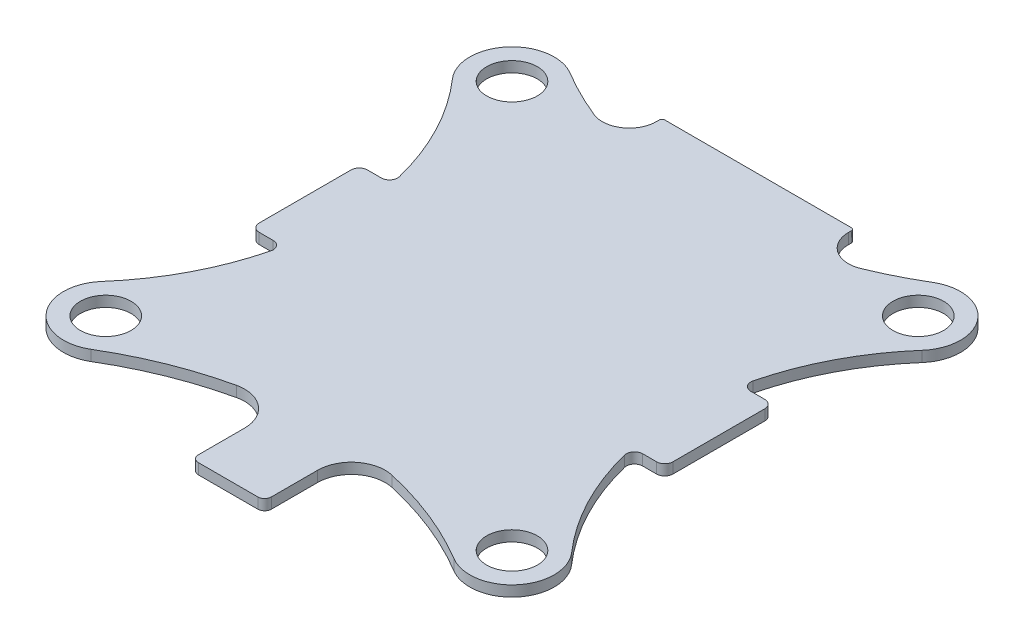
SolidWorks part; units mm, degrees
ref_plane "Front Plane" through (0, 0, 0) normal (0, 0, 1) x (1, 0, 0)
ref_plane "Top Plane" through (0, 0, 0) normal (0, 1, 0) x (1, 0, 0)
ref_plane "Right Plane" through (0, 0, 0) normal (1, 0, 0) x (0, 0, -1)
sketch "Sketch1" plane through (0, 0, 0) normal (0, 1, 0) x (1, 0, 0)
  line L0 (-19.083, 19.083) -> (19.083, -19.083) construction
  line L1 (-15.875, -17.78) -> (15.875, -17.78) construction
  line L2 (-15.875, -17.78) -> (-15.875, 17.78) construction
  line L3 (-15.875, 17.78) -> (15.875, 17.78) construction
  line L4 (15.875, -17.78) -> (15.875, 17.78) construction
  line L5 (-19.083, -19.083) -> (19.083, 19.083) construction
  line L6 (-21.8894, -16.2767) -> (-16.2767, -21.8894) construction
  line L7 (0, -17.78) -> (0, 17.78) construction
  line L8 (-15.875, 0) -> (15.875, 0) construction
  line L9 (21.8894, -16.2767) -> (16.2767, -21.8894) construction
  line L10 (-21.8894, 16.2767) -> (-16.2767, 21.8894) construction
  line L11 (21.8894, 16.2767) -> (16.2767, 21.8894) construction
  line L12 (-17.3519, -5.08) -> (-18.669, -5.08)
  line L13 (-19.431, -4.318) -> (-19.431, 4.318)
  line L14 (-18.669, 5.08) -> (-17.3519, 5.08)
  line L15 (18.669, 5.08) -> (17.3519, 5.08)
  line L16 (19.431, -4.318) -> (19.431, 4.318)
  line L17 (-3.429, -21.6901) -> (-3.429, -26.035)
  line L18 (-2.794, -26.67) -> (2.794, -26.67)
  line L19 (3.429, -26.035) -> (3.429, -21.6901)
  line L20 (-9.017, 22.5811) -> (-9.017, 22.86)
  line L21 (-8.763, 23.114) -> (8.763, 23.114)
  line L22 (9.017, 22.86) -> (9.017, 22.5811)
  line L28 (17.3519, -5.08) -> (18.669, -5.08)
  circle A0 centre (-19.083, -19.083) radius 3.9688 construction
  circle A1 centre (19.083, -19.083) radius 3.9688 construction
  circle A2 centre (19.083, 19.083) radius 3.9688 construction
  circle A3 centre (-19.083, 19.083) radius 3.9688 construction
  arc A4 (-22.0682, 16.4678) -> (-22.0682, -16.4678) centre (-40.8655, 0) cw construction
  arc A5 (-17.0457, 22.489) -> (17.0457, 22.489) centre (0, 50.9859) ccw construction
  arc A6 (-17.0457, -22.489) -> (17.0457, -22.489) centre (0, -50.9859) cw construction
  arc A7 (22.0682, 16.4678) -> (22.0682, -16.4678) centre (40.8655, 0) ccw construction
  arc A8 (-22.0682, 16.4678) -> (-17.0457, 22.489) centre (-19.083, 19.083) cw
  arc A9 (17.0457, 22.489) -> (22.0682, 16.4678) centre (19.083, 19.083) cw
  arc A10 (22.0682, -16.4678) -> (17.0457, -22.489) centre (19.083, -19.083) cw
  arc A11 (-22.0682, -16.4678) -> (-17.0457, -22.489) centre (-19.083, -19.083) ccw
  circle A12 centre (-19.083, -19.083) radius 2.3813
  circle A13 centre (19.083, -19.083) radius 2.3813
  circle A14 centre (19.083, 19.083) radius 2.3813
  circle A15 centre (-19.083, 19.083) radius 2.3813
  arc A16 (-22.0682, -16.4678) -> (-16.6123, -6.0257) centre (-40.8655, 0) ccw
  arc A17 (-17.3519, -5.08) -> (-16.6123, -6.0257) centre (-17.3519, -5.842) cw
  arc A18 (-22.0682, 16.4678) -> (-16.6123, 6.0257) centre (-40.8655, 0) cw
  arc A19 (-16.6123, 6.0257) -> (-17.3519, 5.08) centre (-17.3519, 5.842) cw
  arc A20 (-18.669, 5.08) -> (-19.431, 4.318) centre (-18.669, 4.318) ccw
  arc A21 (-19.431, -4.318) -> (-18.669, -5.08) centre (-18.669, -4.318) ccw
  arc A22 (16.6123, 6.0257) -> (17.3519, 5.08) centre (17.3519, 5.842) ccw
  arc A23 (22.0682, 16.4678) -> (16.6123, 6.0257) centre (40.8655, 0) ccw
  arc A24 (22.0682, -16.4678) -> (16.6123, -6.0257) centre (40.8655, 0) cw
  arc A25 (17.3519, -5.08) -> (16.6123, -6.0257) centre (17.3519, -5.842) ccw
  arc A26 (19.431, -4.318) -> (18.669, -5.08) centre (18.669, -4.318) cw
  arc A27 (18.669, 5.08) -> (19.431, 4.318) centre (18.669, 4.318) cw
  arc A28 (-17.0457, -22.489) -> (-7.3022, -18.5929) centre (0, -50.9859) cw
  arc A29 (17.0457, -22.489) -> (7.3022, -18.5929) centre (0, -50.9859) ccw
  arc A30 (-7.3022, -18.5929) -> (-3.429, -21.6901) centre (-6.604, -21.6901) cw
  arc A31 (7.3022, -18.5929) -> (3.429, -21.6901) centre (6.604, -21.6901) ccw
  arc A32 (-3.429, -26.035) -> (-2.794, -26.67) centre (-2.794, -26.035) ccw
  arc A33 (3.429, -26.035) -> (2.794, -26.67) centre (2.794, -26.035) cw
  arc A34 (-17.0457, 22.489) -> (-12.5142, 20.2284) centre (0, 50.9859) ccw
  arc A35 (17.0457, 22.489) -> (12.5142, 20.2284) centre (0, 50.9859) cw
  arc A36 (-9.017, 22.5811) -> (-12.5142, 20.2284) centre (-11.557, 22.5811) cw
  arc A37 (9.017, 22.5811) -> (12.5142, 20.2284) centre (11.557, 22.5811) ccw
  arc A38 (-8.763, 23.114) -> (-9.017, 22.86) centre (-8.763, 22.86) ccw
  arc A39 (8.763, 23.114) -> (9.017, 22.86) centre (8.763, 22.86) cw
  point P4 (0, 17.78)
  point P6 (15.875, 0)
  point P11 (0, 0)
  point P12 (0, 0)
  point P19 (-19.083, -19.083)
  point P60 (-19.431, 5.08)
  point P63 (-19.431, -5.08)
  point P72 (19.431, -5.08)
  point P73 (19.431, 5.08)
  point P82 (3.429, -17.9575)
  point P85 (-3.429, -26.67)
  point P88 (3.429, -26.67)
  point P95 (-9.017, 19.0277)
  point P98 (9.017, 19.0277)
  point P100 (0, 0)
  point P102 (-9.017, 23.114)
  point P105 (9.017, 23.114)
  dimension "D3" = 7.9375
  dimension "D8" = 0.762
  dimension "D9" = 0.762
  dimension "D10" = 0.762
  dimension "D11" = 0.762
  dimension "D14" = 3.175
  dimension "D15" = 3.175
  dimension "D16" = 0.635
  dimension "D17" = 0.635
  dimension "D20" = 2.54
  dimension "D21" = 2.54
  dimension "D22" = 4.7625
  dimension "D23" = 0.254
  dimension "D24" = 0.254
  dimension "D1" = 31.75
  dimension "D2" = 35.56
  dimension "D4" = 53.975
  dimension "D5" = 3.556
  dimension "D6" = 5.08
  dimension "D7" = 5.08
  dimension "D12" = 6.858
  dimension "D13" = 8.89
  dimension "D18" = 5.334
  dimension "D19" = 18.034
extrude "Boss-Extrude2" add sketch "Sketch1" along normal blind 1 contours A12 | A13 | A14 | A15 | A28 A30 L17 A32 L18 A33 L19 A31 A29 A10 A24 A25 L28 A26 L16 A27 L15 A22 A23 A9 A35 A37 L22 A39 L21 A38 L20 A36 A34 A8 A18 A19 L14 A20 L13 A21 L12 A17 A16 A11 region at (-19.083, 0, 19.083) region at (19.083, 0, 19.083) region at (19.083, 0, -19.083) region at (-19.083, 0, -19.083)
